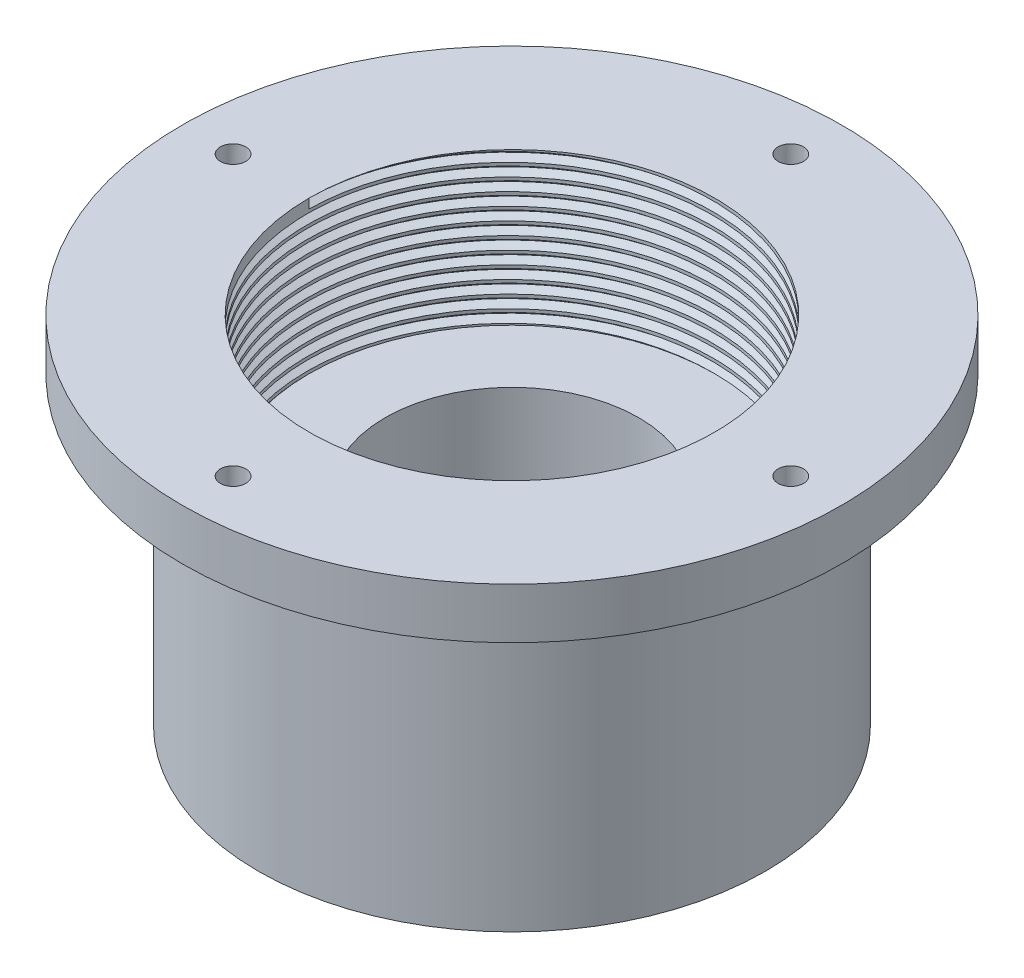
SolidWorks part; units mm, degrees
ref_plane "Front Plane" through (0, 0, 0) normal (0, 0, 1) x (1, 0, 0)
ref_plane "Top Plane" through (0, 0, 0) normal (0, 1, 0) x (1, 0, 0)
ref_plane "Right Plane" through (0, 0, 0) normal (1, 0, 0) x (0, 0, -1)
sketch "Sketch1" plane through (0, 0, 0) normal (0, 1, 0) x (1, 0, 0)
  circle A0 centre (0, 0) radius 50
extrude "Boss-Extrude1" add sketch "Sketch1" along normal blind 60
sketch "Sketch2" plane through (0, 60, 0) normal (0, 1, 0) x (1, 0, 0)
  circle A0 centre (0, 0) radius 65
extrude "Boss-Extrude2" add sketch "Sketch2" along normal blind 10
sketch "Sketch3" plane through (0, 70, 0) normal (0, 1, 0) x (1, 0, 0)
  circle A0 centre (0, 0) radius 40
extrude "Cut-Extrude1" cut sketch "Sketch3" against normal blind 30
sketch "Sketch4" plane through (0, 40, 0) normal (0, 1, 0) x (1, 0, 0)
  circle A0 centre (0, 0) radius 25
extrude "Cut-Extrude2" cut sketch "Sketch4" against normal blind 20
sketch "Sketch5" plane through (0, 20, 0) normal (0, 1, 0) x (1, 0, 0)
  circle A0 centre (0, 0) radius 10
extrude "Cut-Extrude4" cut sketch "Sketch5" against normal through all
sketch "Sketch6" plane through (0, 0, 0) normal (0, -1, 0) x (-1, 0, 0)
  circle A0 centre (0, -20) radius 2.5
  circle A1 centre (-20, 0) radius 2.5
  circle A2 centre (0, 20) radius 2.5
  circle A3 centre (20, 0) radius 2.5
  point P12 (0, 0)
  dimension "D1" = 20
  dimension "D2" = 4
extrude "Cut-Extrude5" cut sketch "Sketch6" against normal through all
sketch "Sketch7" plane through (0, 70, 0) normal (0, 1, 0) x (1, 0, 0)
  circle A0 centre (0, 55) radius 2.5
  circle A1 centre (55, 0) radius 2.5
  circle A2 centre (0, -55) radius 2.5
  circle A3 centre (-55, 0) radius 2.5
  point P12 (0, 0)
  dimension "D1" = 55
  dimension "D2" = 4
extrude "Cut-Extrude6" cut sketch "Sketch7" against normal through all
thread "Thread1" pitch 2.5 method cut profile "Thread Profile1" start angle 0, offset 0, length 0, pitch 2.5, diameter 80
ref_plane "Plane1" through (-40, 70, 0) normal (0, 0, 1) x (-1, 0, 0)
sketch "Thread Profile1" plane through (-40, 70, 0) normal (0, 0, 1) x (-1, 0, 0)
  line L0 (0, 0) -> (0, 2.5) construction
  line L1 (0, 0) -> (1.3532, 0.7812)
  line L2 (1.3532, 0.7812) -> (1.3532, 1.0937)
  line L3 (1.3532, 1.0937) -> (0, 1.875)
  line L4 (1.3532, 0.9375) -> (0, 0.9375) construction
  line L11 (0, 0) -> (0, 1.875)
  point P2 (0, 0)
  dimension "Pitch" = 2.5
  dimension "Profile_Angle" = 60
  dimension "Profile_Land" = 0.3125
  dimension "Profile_Height" = 1.3532
